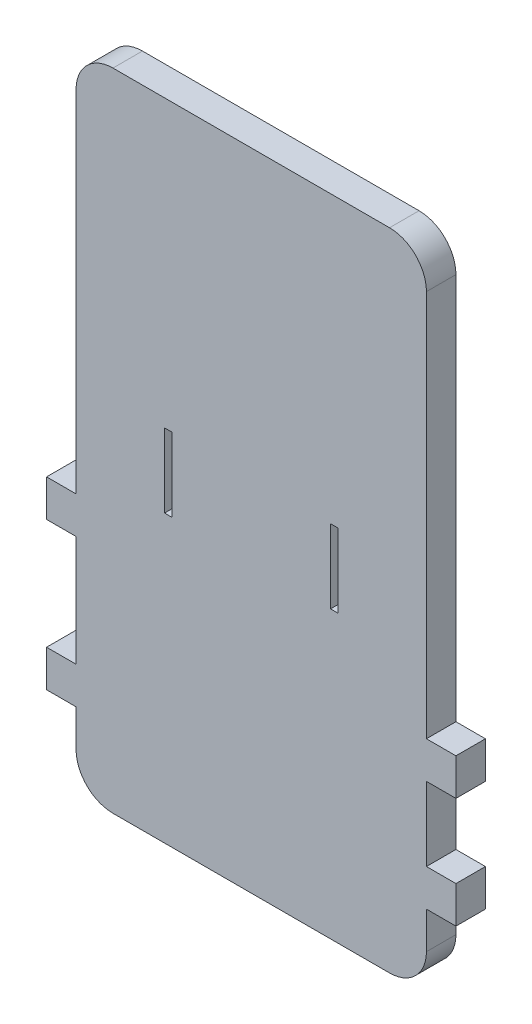
SolidWorks part; units mm, degrees
material "Beech"
ref_plane "Front" through (0, 0, 0) normal (0, 0, 1) x (1, 0, 0)
ref_plane "Top" through (0, 0, 0) normal (0, 1, 0) x (1, 0, 0)
ref_plane "Right" through (0, 0, 0) normal (1, 0, 0) x (0, 0, -1)
sketch "Sketch1" plane through (0, 0, 0) normal (0, 0, 1) x (1, 0, 0)
  line L0 (0, 22.3837) -> (0, -18.314) construction
  line L1 (-37.5, -87.5) -> (37.5, -87.5)
  line L2 (-47.5, -77.5) -> (-47.5, 77.5)
  line L3 (-37.5, 87.5) -> (37.5, 87.5)
  line L4 (47.5, -77.5) -> (47.5, 77.5)
  line L5 (-47.5, -87.5) -> (47.5, 87.5) construction
  line L6 (-47.5, 87.5) -> (47.5, -87.5) construction
  line L7 (-21.5, 10) -> (-23.5, 10)
  line L8 (21.5, -10) -> (23.5, -10)
  line L9 (21.5, -10) -> (21.5, 10)
  line L10 (21.5, 10) -> (23.5, 10)
  line L11 (23.5, -10) -> (23.5, 10)
  line L12 (21.5, -10) -> (23.5, 10) construction
  line L13 (21.5, 10) -> (23.5, -10) construction
  line L14 (-23.5, -10) -> (-23.5, 10)
  line L15 (-21.5, -10) -> (-23.5, -10)
  line L16 (-21.5, -10) -> (-21.5, 10)
  line L17 (47.5, 82.5) -> (-47.5, 82.5) construction
  line L18 (11.0081, 0) -> (-11.7376, 0) construction
  arc A0 (-37.5, -87.5) -> (-47.5, -77.5) centre (-37.5, -77.5) cw
  arc A1 (37.5, -87.5) -> (47.5, -77.5) centre (37.5, -77.5) ccw
  arc A2 (-47.5, 77.5) -> (-37.5, 87.5) centre (-37.5, 77.5) cw
  arc A3 (37.5, 87.5) -> (47.5, 77.5) centre (37.5, 77.5) cw
  point P0 (0, 0)
  point P8 (22.5, 0)
  dimension "D7" = 10
  dimension "D1" = 175
  dimension "D2" = 95
  dimension "D3" = 2
  dimension "D4" = 22.5
  dimension "D5" = 20
  dimension "D6" = 5
extrude "Boss-Extrude1" add sketch "Sketch1" along normal blind 8 contours L1 L4 L3 L2 L16 L15 L14 L7 L11 L8 L9 L10 region at (0, 0, 0)
sketch "Sketch3" plane through (-47.5, 0, 0) normal (-1, 0, 0) x (0, 0, 1)
  line L0 (0, -77.5) -> (0, 77.5) construction
  line L1 (0, -57.5) -> (8, -57.5)
  line L2 (0, -57.5) -> (0, -67.5)
  line L3 (0, -67.5) -> (8, -67.5)
  line L4 (8, -57.5) -> (8, -67.5)
  line L5 (0, -57.5) -> (8, -67.5) construction
  line L6 (0, -67.5) -> (8, -57.5) construction
  line L7 (8, -77.5) -> (8, 77.5) construction
  line L9 (8, -87.5) -> (0, -87.5) construction
  line L11 (0, -27.5) -> (8, -27.5)
  line L12 (0, -27.5) -> (0, -17.5)
  line L13 (0, -17.5) -> (8, -17.5)
  line L14 (8, -27.5) -> (8, -17.5)
  line L15 (0, -27.5) -> (8, -17.5) construction
  line L16 (0, -17.5) -> (8, -27.5) construction
  point P4 (4, -62.5)
  point P15 (4, -22.5)
  dimension "D1" = 20
  dimension "D2" = 10
  dimension "D3" = 10
  dimension "D4" = 50
extrude "Boss-Extrude2" add sketch "Sketch3" along normal blind 8
sketch "Sketch4" plane through (47.5, 0, 0) normal (1, 0, 0) x (0, 0, -1)
  line L0 (-8, -77.5) -> (-8, 77.5) construction
  line L1 (-8, -67.5) -> (0, -67.5)
  line L2 (-8, -67.5) -> (-8, -57.5)
  line L3 (-8, -57.5) -> (0, -57.5)
  line L4 (0, -67.5) -> (0, -57.5)
  line L5 (-8, -67.5) -> (0, -57.5) construction
  line L6 (-8, -57.5) -> (0, -67.5) construction
  line L7 (0, -77.5) -> (0, 77.5) construction
  line L8 (-8, -87.5) -> (0, -87.5) construction
  line L9 (-8, -27.5) -> (0, -27.5)
  line L10 (0, -37.5) -> (0, -27.5)
  line L11 (-8, -37.5) -> (0, -37.5)
  line L12 (-8, -37.5) -> (-8, -27.5)
  point P4 (-4, -62.5)
  dimension "D1" = 20
  dimension "D2" = 10
  dimension "D4" = 20
  dimension "D3" = 2
extrude "Boss-Extrude3" add sketch "Sketch4" along normal blind 8
